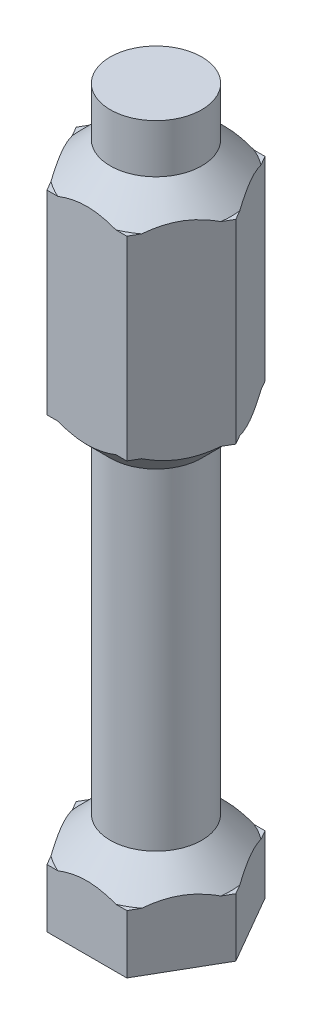
SolidWorks part; units mm, degrees
ref_plane "Front Plane" through (0, 0, 0) normal (0, 0, 1) x (1, 0, 0)
ref_plane "Top Plane" through (0, 0, 0) normal (0, 1, 0) x (1, 0, 0)
ref_plane "Right Plane" through (0, 0, 0) normal (1, 0, 0) x (0, 0, -1)
sketch "Sketch1" plane through (0, 0, 0) normal (0, 1, 0) x (1, 0, 0)
  line L1 (2.0496, -3.55) -> (4.0992, 0)
  line L2 (4.0992, 0) -> (2.0496, 3.55)
  line L3 (2.0496, 3.55) -> (-2.0496, 3.55)
  line L4 (-2.0496, 3.55) -> (-4.0992, 0)
  line L5 (-4.0992, 0) -> (-2.0496, -3.55)
  line L6 (-2.0496, -3.55) -> (2.0496, -3.55)
  circle A0 centre (0, 0) radius 3.55 construction
  dimension "D1" = 7.1
extrude "Boss-Extrude1" add sketch "Sketch1" along normal blind 3
sketch "Sketch2" plane through (0, 3, 0) normal (0, 1, 0) x (1, 0, 0)
  circle A0 centre (0, 0) radius 2.35
  dimension "D1" = 4.7
extrude "Boss-Extrude2" add sketch "Sketch2" along normal blind 20
extrude "Boss-Extrude3" add sketch "Sketch1<2>" along normal blind 10 from surface starting at face at (0, 23, 2.35)
sketch "Sketch1<2>" plane through (0, 0, 0) normal (0, 1, 0) x (1, 0, 0) same geometry as "Sketch1"
extrude "Boss-Extrude4" add sketch "Sketch2<2>" along normal blind 4 from surface starting at face at (0, 33, 0)
sketch "Sketch2<2>" plane through (0, 3, 0) normal (0, 1, 0) x (1, 0, 0) same geometry as "Sketch2"
chamfer "Chamfer1" distance 1.5 angle 45 3 edges at (0, 23, 2.35) (0, 3, 2.35) (0, 33, -2.35)
